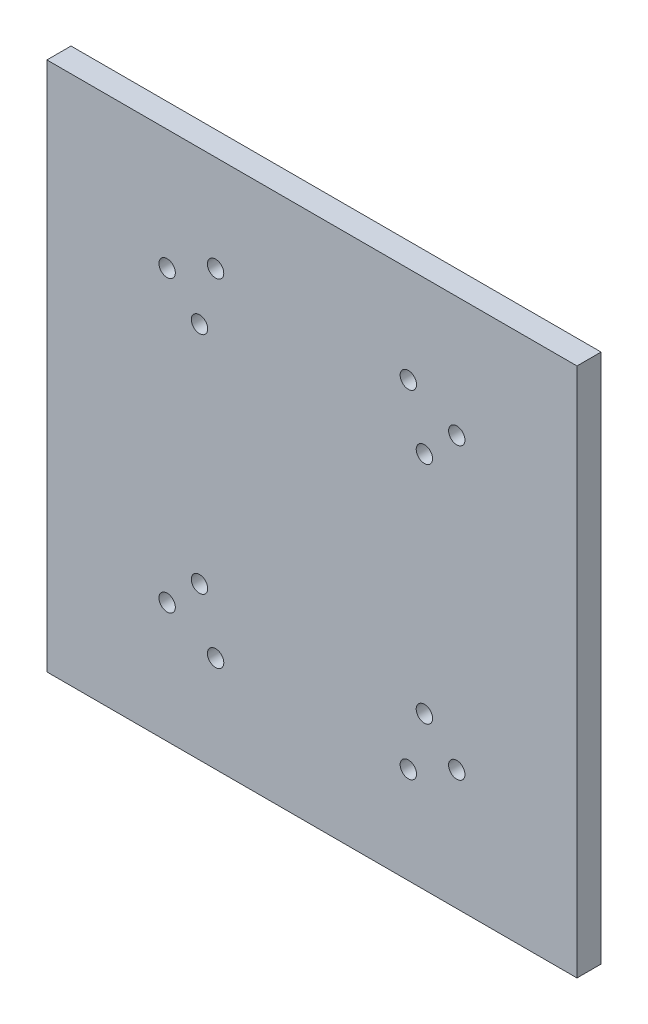
SolidWorks part; units mm, degrees
ref_plane "Ebene vorne" through (0, 0, 0) normal (0, 0, 1) x (1, 0, 0)
ref_plane "Ebene oben" through (0, 0, 0) normal (0, 1, 0) x (1, 0, 0)
ref_plane "Ebene rechts" through (0, 0, 0) normal (1, 0, 0) x (0, 0, -1)
sketch "Skizze1" plane through (0, 0, 0) normal (0, 0, 1) x (1, 0, 0)
  line L1 (-110, -110) -> (110, -110)
  line L2 (-110, -110) -> (-110, 110)
  line L3 (-110, 110) -> (110, 110)
  line L4 (110, -110) -> (110, 110)
  line L5 (-110, -110) -> (110, 110) construction
  line L6 (-110, 110) -> (110, -110) construction
  point P0 (0, 0)
  dimension "D1" = 220
extrude "Aufsatz-Linear austragen1" add sketch "Skizze1" along normal blind 10
ref_axis "Achse1" through (0, 0, -85.4779) along (0, 0, 1)
sketch "Skizze2" plane through (0, 0, 10) normal (0, 0, 1) x (1, 0, 0)
  line L0 (0, 0) -> (30.2681, 0) construction
  line L1 (0, 0) -> (0, 34.1137) construction
  line L2 (0, 0) -> (91.4416, 91.4416) construction
  line L3 (0, 0) -> (91.4416, -91.4416) construction
  line L4 (0, 0) -> (-91.4416, -91.4416) construction
  line L5 (0, 0) -> (-91.4416, 91.4416) construction
  circle A0 centre (46.669, 46.669) radius 3.4
  circle A1 centre (46.669, -46.669) radius 3.4
  circle A2 centre (-46.669, -46.669) radius 3.4
  circle A3 centre (-46.669, 46.669) radius 3.4
  circle A4 centre (0, 0) radius 66 construction
  circle A5 centre (0, 0) radius 85 construction
  circle A6 centre (60.1041, 60.1041) radius 3.4
  circle A7 centre (60.1041, -60.1041) radius 3.4
  circle A8 centre (0, 0) radius 85 construction
  circle A9 centre (-60.1041, -60.1041) radius 3.4
  circle A10 centre (0, 0) radius 85 construction
  circle A11 centre (-60.1041, 60.1041) radius 3.4
  circle A12 centre (0, 0) radius 85 construction
  point P15 (0, 0)
  point P33 (0, 0)
  dimension "D1" = 6.8
  dimension "D2" = 132
  dimension "D5" = 170
  dimension "D6" = 6.8
  dimension "D4" = 45
  dimension "D3" = 4
  dimension "D7" = 4
extrude "Schnitt-Linear austragen1" cut sketch "Skizze2" against normal through all
sketch "Skizze3" plane through (0, 0, 10) normal (0, 0, 1) x (1, 0, 0)
  line L0 (0, 0) -> (171.4432, 0) construction
  line L1 (0, 0) -> (0, 120.5012) construction
  circle A0 centre (40, -70) radius 3.4
  circle A1 centre (-40, -70) radius 3.4
  circle A2 centre (40, 70) radius 3.4
  circle A3 centre (-40, 70) radius 3.4
  dimension "D1" = 6.8
  dimension "D2" = 140
  dimension "D3" = 80
extrude "Schnitt-Linear austragen2" cut sketch "Skizze3" against normal through all
